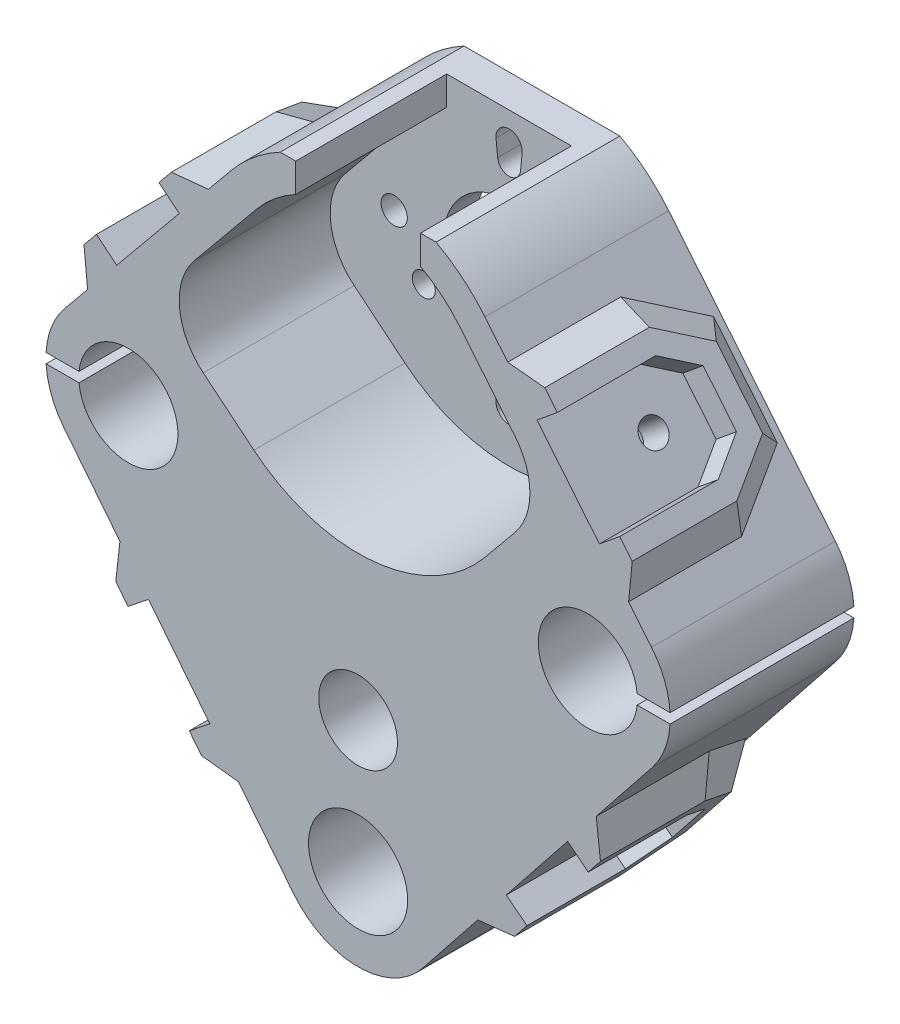
SolidWorks part; units mm, degrees
ref_plane "Płaszczyzna przednia" through (0, 0, 0) normal (0, 0, 1) x (1, 0, 0)
ref_plane "Płaszczyzna górna" through (0, 0, 0) normal (0, 1, 0) x (1, 0, 0)
ref_plane "Płaszczyzna prawa" through (0, 0, 0) normal (1, 0, 0) x (0, 0, -1)
sketch "Szkic1" plane through (0, 0, 0) normal (0, 0, 1) x (1, 0, 0)
  line L0 (-44.6984, 31.9651) -> (-19.3196, 62.8668)
  line L1 (19.3196, 62.8668) -> (44.6984, 31.9651)
  line L2 (9.8216, -27.8127) -> (44.8216, 16.1873)
  line L3 (-9.8216, -27.8127) -> (-44.8216, 16.1873)
  line L4 (0, 47) -> (0, -49.1477) construction
  line L5 (-42.5127, 24.75) -> (-47.5276, 24.75)
  line L6 (-42.5127, 23.25) -> (-47.5276, 23.25)
  line L7 (42.5127, 24.75) -> (47.5276, 24.75)
  line L8 (42.5127, 23.25) -> (47.5276, 23.25)
  line L9 (-0.75, -27.5127) -> (-0.75, -32.5276)
  line L10 (0.75, -27.5127) -> (0.75, -32.5276)
  line L11 (11.8743, 69) -> (-11.8743, 69)
  circle A0 centre (0, 0) radius 6
  circle A1 centre (0, -20) radius 7.55
  circle A2 centre (-35, 24) radius 7.55
  circle A3 centre (35, 24) radius 7.55
  circle A4 centre (0, 47) radius 20
  circle A5 centre (-35, 24) radius 12.55
  circle A6 centre (35, 24) radius 12.55
  circle A7 centre (0, -20) radius 12.55
  circle A8 centre (0, 47) radius 25
  dimension "D1" = 44
  dimension "D5" = 15.1
  dimension "D6" = 12
  dimension "D7" = 40
  dimension "D2" = 35
  dimension "D3" = 35
  dimension "D4" = 20
  dimension "D8" = 47
  dimension "D9" = 5
  dimension "D10" = 1.5
  dimension "D11" = 1.5
  dimension "D12" = 22
extrude "Dodanie-wyciągnięcie1" add sketch "Szkic1" along normal blind 28 contours A5 A2 | A8 L0 A5 L3 A7 L2 A6 L1 A0 | A8 A4 | A6 A3 | A7 A1 | A4 | A8 L4 A0 A7 L2 A6 L1 | A7 L4 A1 L10 | L4 A4 L11 A8 | L4 A7 L9 A1
sketch "Szkic2" plane through (0, 0, 28) normal (0, 0, 1) x (1, 0, 0)
  line L0 (19.3196, 31.1332) -> (32.3506, 47)
  line L1 (-15.8668, 27.6804) -> (-35.1863, 43.5472)
  line L10 (-44.8216, 16.1873) -> (-9.8216, -27.8127)
  line L13 (9.8216, -27.8127) -> (44.8216, 16.1873)
  line L14 (47.5276, 23.25) -> (42.5127, 23.25)
  line L15 (42.5127, 24.75) -> (47.5276, 24.75)
  line L16 (44.6984, 31.9651) -> (19.3196, 62.8668)
  line L17 (-19.3196, 62.8668) -> (-44.6984, 31.9651)
  line L18 (-47.5276, 24.75) -> (-42.5127, 24.75)
  line L19 (-42.5127, 23.25) -> (-47.5276, 23.25)
  line L20 (-44.8216, 16.1873) -> (-9.8216, -27.8127)
  line L23 (9.8216, -27.8127) -> (44.8216, 16.1873)
  line L24 (47.5276, 23.25) -> (42.5127, 23.25)
  line L25 (42.5127, 24.75) -> (47.5276, 24.75)
  line L26 (44.6984, 31.9651) -> (19.3196, 62.8668)
  line L27 (-19.3196, 62.8668) -> (-44.6984, 31.9651)
  line L28 (-47.5276, 24.75) -> (-42.5127, 24.75)
  line L29 (-42.5127, 23.25) -> (-47.5276, 23.25)
  line L33 (11.8743, 69) -> (-11.8743, 69)
  line L34 (11.8743, 69) -> (-11.8743, 69)
  circle A0 centre (0, 47) radius 25
  arc A10 (-9.8216, -27.8127) -> (9.8216, -27.8127) centre (0, -20) ccw
  arc A13 (44.8216, 16.1873) -> (47.5276, 23.25) centre (35, 24) ccw
  arc A14 (42.5127, 24.75) -> (42.5127, 23.25) centre (35, 24) ccw
  arc A15 (47.5276, 24.75) -> (44.6984, 31.9651) centre (35, 24) ccw
  arc A16 (19.3196, 62.8668) -> (11.8743, 69) centre (0, 47) ccw
  arc A17 (-44.6984, 31.9651) -> (-47.5276, 24.75) centre (-35, 24) ccw
  arc A18 (-42.5127, 23.25) -> (-42.5127, 24.75) centre (-35, 24) ccw
  arc A19 (-47.5276, 23.25) -> (-44.8216, 16.1873) centre (-35, 24) ccw
  arc A20 (-9.8216, -27.8127) -> (9.8216, -27.8127) centre (0, -20) ccw
  arc A23 (44.8216, 16.1873) -> (47.5276, 23.25) centre (35, 24) ccw
  arc A24 (42.5127, 24.75) -> (42.5127, 23.25) centre (35, 24) ccw
  arc A25 (47.5276, 24.75) -> (44.6984, 31.9651) centre (35, 24) ccw
  arc A26 (19.3196, 62.8668) -> (11.8743, 69) centre (0, 47) ccw
  arc A27 (-44.6984, 31.9651) -> (-47.5276, 24.75) centre (-35, 24) ccw
  arc A28 (-42.5127, 23.25) -> (-42.5127, 24.75) centre (-35, 24) ccw
  arc A29 (-47.5276, 23.25) -> (-44.8216, 16.1873) centre (-35, 24) ccw
  arc A32 (-11.8743, 69) -> (-19.3196, 62.8668) centre (0, 47) ccw
  arc A33 (-11.8743, 69) -> (-19.3196, 62.8668) centre (0, 47) ccw
  line M35 (44.6984, 31.9651) -> (19.3196, 62.8668)
  arc M36 (19.3196, 62.8668) -> (11.8743, 69) centre (0, 47) ccw
  line M37 (-19.3196, 62.8668) -> (-44.6984, 31.9651)
  dimension "D1" = 0
extrude "Wytnij-wyciągnięcie1" cut sketch "Szkic2" against normal blind 23 contours A0 L1 M37 | A0 M36 | A0 L0 M35
sketch "Szkic3" plane through (0, 0, 5) normal (0, 0, 1) x (1, 0, 0)
  circle A0 centre (0, 47) radius 10
  circle A1 centre (0, 47) radius 15 construction
  circle A2 centre (0, 62) radius 1.75
  circle A3 centre (12.9904, 39.5) radius 1.75
  circle A4 centre (-12.9904, 39.5) radius 1.75
  point P13 (0, 47)
  dimension "D1" = 47
  dimension "D2" = 20
  dimension "D3" = 30
  dimension "D4" = 3.5
  dimension "D5" = 3
extrude "Wytnij-wyciągnięcie2" cut sketch "Szkic3" against normal blind 23
sketch "Szkic4" plane through (0, 0, 5) normal (0, 0, 1) x (1, 0, 0)
  line L0 (32.3506, 47) -> (19.3196, 62.8668) construction
  line L1 (-19.3196, 62.8668) -> (-35.1863, 43.5472) construction
  line L2 (32.3506, 47) -> (19.3196, 62.8668)
  line L3 (-19.3196, 62.8668) -> (-35.1863, 43.5472)
  line L4 (-15.4557, 59.6934) -> (-31.3224, 40.3738)
  line L5 (28.4867, 43.8266) -> (15.4557, 59.6934)
  line L6 (-9.4995, 64.6) -> (-9.4995, 69)
  line L7 (11.8743, 69) -> (-11.8743, 69) construction
  line L8 (9.4995, 64.6) -> (9.4995, 69)
  line L9 (-15.8668, 27.6804) -> (-35.1863, 43.5472) construction
  line L10 (19.3196, 31.1332) -> (32.3506, 47) construction
  line L11 (-15.8668, 27.6804) -> (-35.1863, 43.5472)
  line L12 (19.3196, 31.1332) -> (32.3506, 47)
  line L13 (28.4867, 43.8266) -> (29.1155, 43.0609)
  arc A0 (-11.8743, 69) -> (-19.3196, 62.8668) centre (0, 47) ccw construction
  arc A1 (19.3196, 62.8668) -> (11.8743, 69) centre (0, 47) ccw construction
  arc A2 (-11.8743, 69) -> (-19.3196, 62.8668) centre (0, 47) ccw
  arc A3 (19.3196, 62.8668) -> (11.8743, 69) centre (0, 47) ccw
  arc A4 (-9.4995, 64.6) -> (-15.4557, 59.6934) centre (0, 47) ccw
  arc A5 (15.4557, 59.6934) -> (9.4995, 64.6) centre (0, 47) ccw
  line M8 (-35.1863, 43.5472) -> (-15.8668, 27.6804)
  line M11 (32.3506, 47) -> (19.3196, 62.8668)
  arc M12 (19.3196, 62.8668) -> (11.8743, 69) centre (0, 47) ccw
  line M13 (11.8743, 69) -> (-11.8743, 69)
  arc M14 (-11.8743, 69) -> (-19.3196, 62.8668) centre (0, 47) ccw
  line M15 (-19.3196, 62.8668) -> (-35.1863, 43.5472)
  dimension "D1" = 5
extrude "Dodanie-wyciągnięcie2" add sketch "Szkic4" along normal blind 23 contours A4 L6 L4 M13 M14 M15 M8 | A5 L5 L13 L12 L8 M11 M12 M13
fillet "Zaokrąglenie2" radius 10 2 edges at (29.1155, 43.0609, 16.5) (-31.3224, 40.3738, 16.5)
sketch "Szkic5" plane through (0, 0, 0) normal (0, 0, -1) x (-1, 0, 0)
  line L0 (0, 47) -> (-39.9534, 47) construction
  line L1 (0, 47) -> (0, 64.5) construction
  line L2 (-1.99, 64.3) -> (-1.7412, 61.825)
  line L3 (1.99, 64.3) -> (1.7412, 61.825)
  circle A0 centre (0, 47) radius 17.5 construction
  circle A1 centre (0, 64.5) radius 2
  circle A2 centre (17.5, 47) radius 2
  circle A3 centre (0, 29.5) radius 2
  circle A4 centre (-17.5, 47) radius 2
  circle A5 centre (0, 62) radius 1.75 construction
  circle A6 centre (0, 62) radius 1.75
  point P15 (0, 47)
  circle M5 centre (0, 62) radius 1.75
  dimension "D1" = 4
  dimension "D2" = 35
  dimension "D3" = 90
  dimension "D4" = 4
extrude "Wytnij-wyciągnięcie3" cut sketch "Szkic5" against normal blind 10 contours A4 | A2 | A3 | A1 M5 | A1 L2 M5 | A1 L3 M5 | A1 M5 | A1 M5
sketch "Szkic6" plane through (42.3713, 34.7986, 0) normal (0.7728, 0.6347, 0) x (0, 0, -1)
  line L0 (-28, 23.8333) -> (-13, 23.8333)
  line L1 (-28, 36.3208) -> (-28, -3.6667) construction
  line L2 (-13, 23.8333) -> (-8, 20.3333)
  line L3 (-8, 20.3333) -> (-8, 12.3333)
  line L4 (-8, 12.3333) -> (-13, 8.8333)
  line L5 (-13, 8.8333) -> (-28, 8.8333)
  line L6 (-28, -3.6667) -> (0, -3.6667) construction
  line L8 (-28, 26.8333) -> (-12.0543, 26.8333)
  line L9 (-12.0543, 26.8333) -> (-5, 21.8953)
  line L10 (-5, 21.8953) -> (-5, 10.7714)
  line L11 (-5, 10.7714) -> (-12.0543, 5.8333)
  line L12 (-12.0543, 5.8333) -> (-28, 5.8333)
  line L14 (-31, 5.8333) -> (-31, 26.8333) construction
  line L15 (-28, 8.8333) -> (-28, 23.8333) construction
  line L16 (-28, 5.8333) -> (-28, 26.8333)
  line L17 (-31, 26.8333) -> (-12.0543, 26.8333) construction
  line L18 (-12.0543, 5.8333) -> (-31, 5.8333) construction
  point P5 (-8, 16.3333)
  line M7 (-28, 36.3208) -> (-28, -3.6667)
  dimension "D1" = 20
  dimension "D2" = 15
  dimension "D3" = 8
  dimension "D4" = 20
  dimension "D5" = 15
  dimension "D6" = 3
extrude "Dodanie-wyciągnięcie3" add sketch "Szkic6" along normal blind 4 contours L12 L11 L10 L9 L8 L0 L2 L3 L4 L5 M7
chamfer "Sfazowanie1" distance 4 angle 45 5 edges at (25.341, 55.535, 20.0272) (26.908, 53.627, 8.5272) (32.005, 47.4208, 5) (37.1021, 41.2146, 8.5272) (38.6691, 39.3066, 20.0272)
sketch "Szkic7" plane through (19.5654, -15.5634, 0) normal (0.7826, -0.6225, 0) x (0, 0, -1)
  line L0 (-28, 19.848) -> (-13, 19.848)
  line L1 (-28, -15.652) -> (-28, 40.5708) construction
  line L2 (-13, 19.848) -> (-8, 16.348)
  line L3 (-8, 16.348) -> (-8, 8.348)
  line L4 (-8, 8.348) -> (-13, 4.848)
  line L5 (-13, 4.848) -> (-28, 4.848)
  line L6 (-28, -15.652) -> (0, -15.652) construction
  line L7 (-28, 22.848) -> (-12.0543, 22.848)
  line L8 (-12.0543, 22.848) -> (-5, 17.9099)
  line L9 (-5, 17.9099) -> (-5, 6.786)
  line L10 (-5, 6.786) -> (-12.0543, 1.848)
  line L11 (-12.0543, 1.848) -> (-28, 1.848)
  line L12 (-28, 1.848) -> (-28, 22.848)
  point P5 (-8, 12.348)
  line M8 (-28, 40.5708) -> (-28, -15.652)
  dimension "D1" = 8
  dimension "D2" = 15
  dimension "D3" = 20
  dimension "D4" = 15
  dimension "D5" = 28
  dimension "D6" = 3
extrude "Dodanie-wyciągnięcie4" add sketch "Szkic7" along normal blind 4 contours L11 L10 L9 L8 L7 L0 L2 L3 L4 L5 M8
chamfer "Sfazowanie2" distance 4 angle 45 5 edges at (20.7158, -14.1172, 20.0272) (22.2528, -12.1849, 8.5272) (27.2523, -5.8998, 5) (32.2518, 0.3852, 8.5272) (33.7888, 2.3175, 20.0272)
sketch "Szkic8" plane through (42.3713, 34.7986, 0) normal (0.7728, 0.6347, 0) x (0, 0, -1)
  line L0 (-8, 20.3333) -> (-8, 12.3333) construction
  line L1 (-13, 8.8333) -> (-28, 8.8333) construction
  circle A0 centre (-15, 16.3333) radius 2
  dimension "D1" = 4
  dimension "D2" = 7
  dimension "D3" = 7.5
extrude "Wytnij-wyciągnięcie4" cut sketch "Szkic8" against normal blind 5
sketch "Szkic9" plane through (19.5654, -15.5634, 0) normal (0.7826, -0.6225, 0) x (0, 0, -1)
  line L0 (-13, 4.848) -> (-28, 4.848) construction
  line L1 (-8, 16.348) -> (-8, 8.348) construction
  circle A0 centre (-15, 12.348) radius 2
  point P4 (0, 0)
  dimension "D1" = 4
  dimension "D2" = 7.5
  dimension "D3" = 7
extrude "Wytnij-wyciągnięcie5" cut sketch "Szkic9" against normal blind 5
mirror "Lustro3" about plane through (0, 0, 0) normal (1, 0, 0) of "Wytnij-wyciągnięcie4", "Dodanie-wyciągnięcie3", "Wytnij-wyciągnięcie5", "Dodanie-wyciągnięcie4"
chamfer "Sfazowanie3" distance 4 angle 45 10 edges at (-25.341, 55.535, 20.0272) (-26.908, 53.627, 8.5272) (-32.005, 47.4208, 5) (-37.1021, 41.2146, 8.5272) (-38.6691, 39.3066, 20.0272) (-33.7888, 2.3175, 20.0272) (-32.2518, 0.3852, 8.5272) (-27.2523, -5.8998, 5) (-22.2528, -12.1849, 8.5272) (-20.7158, -14.1172, 20.0272)
